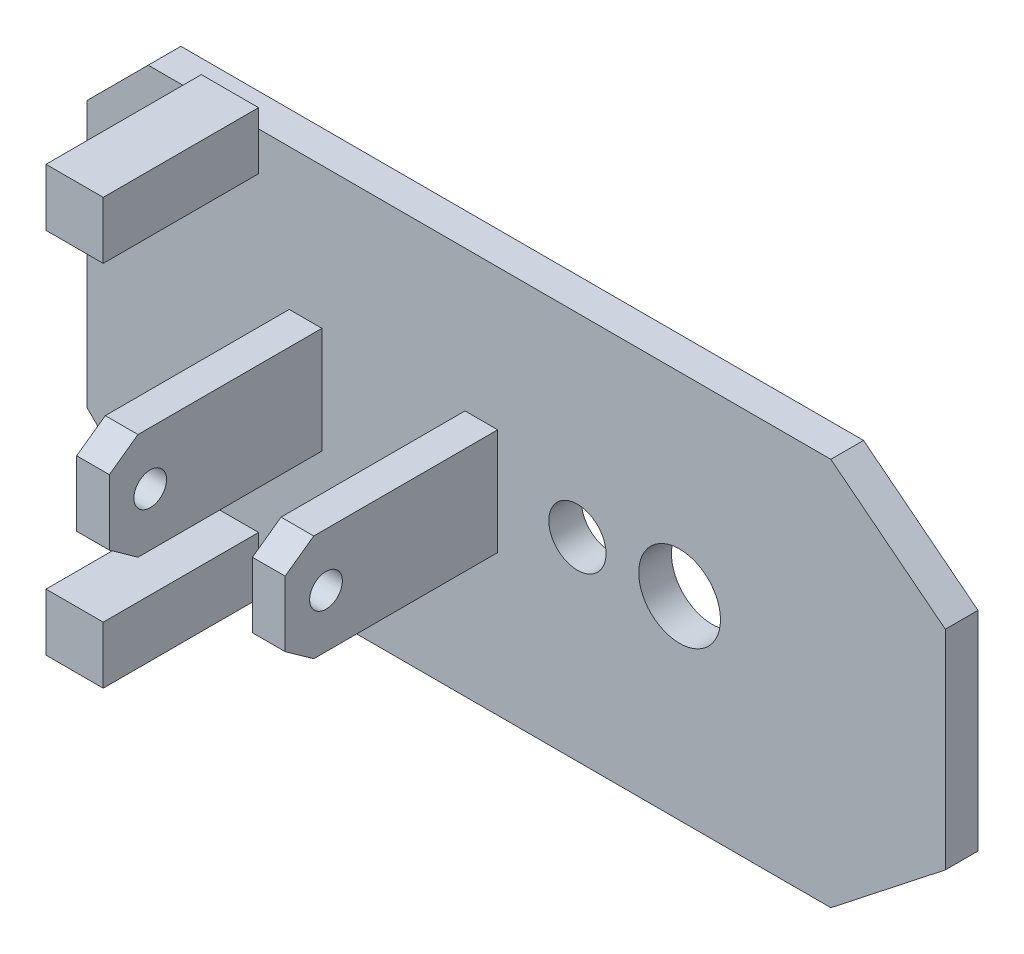
SolidWorks part; units mm, degrees
material "6061-T6 (SS)"
ref_plane "Front Plane" through (0, 0, 0) normal (0, 0, 1) x (1, 0, 0)
ref_plane "Top Plane" through (0, 0, 0) normal (0, 1, 0) x (1, 0, 0)
ref_plane "Right Plane" through (0, 0, 0) normal (1, 0, 0) x (0, 0, -1)
ref_plane "PL_Sole_Plate_base" through (0, 0, -50) normal (0, 0, 1) x (1, 0, 0)
sketch "SK_Sole_Plate" plane through (0, 0, -50) normal (0, 0, 1) x (1, 0, 0)
  line L0 (-60, 47.5) -> (107, 47.5)
  line L1 (107, 47.5) -> (135, 25.5)
  line L2 (135, 25.5) -> (135, -25.5)
  line L3 (135, -25.5) -> (107, -47.5)
  line L4 (107, -47.5) -> (-60, -47.5)
  line L5 (-60, -47.5) -> (-75, -32.5)
  line L6 (-75, -32.5) -> (-75, 32.5)
  line L7 (-75, 32.5) -> (-60, 47.5)
  circle A0 centre (70, 0) radius 10
  circle A1 centre (45, 0) radius 7
  dimension "D17_SK_Sole_Plate" = 20
  dimension "D19_SK_Sole_Plate" = 14
  dimension "P1" = 60
  dimension "P2" = 47.5
  dimension "P3" = 107
  dimension "P4" = 47.5
  dimension "P5" = 135
  dimension "P6" = 25.5
  dimension "P7" = 135
  dimension "P8" = 25.5
  dimension "P9" = 107
  dimension "P10" = 47.5
  dimension "P11" = 60
  dimension "P12" = 47.5
  dimension "P13" = 75
  dimension "P14" = 32.5
  dimension "P15" = 75
  dimension "P16" = 32.5
  dimension "P18" = 70
  dimension "P20" = 45
extrude "Sole_Plate" add sketch "SK_Sole_Plate" along normal blind 8
ref_plane "PL_Clevis_Front_base" through (17.5, 0, 0) normal (1, 0, 0) x (0, 0, -1)
sketch "SK_Clevis_Front" plane through (17.5, 0, 0) normal (1, 0, 0) x (0, 0, -1)
  line L0 (42, 13) -> (42, -13)
  line L1 (42, -13) -> (-3, -13)
  line L2 (-3, -13) -> (-10, -8)
  line L3 (-10, -8) -> (-10, 8)
  line L4 (-10, 8) -> (-3, 13)
  line L5 (-3, 13) -> (42, 13)
  circle A0 centre (0, 0) radius 4
  dimension "D13_SK_Clevis_Front" = 8
  dimension "P1" = 42
  dimension "P2" = 13
  dimension "P3" = 42
  dimension "P4" = 13
  dimension "P5" = 3
  dimension "P6" = 13
  dimension "P7" = 10
  dimension "P8" = 8
  dimension "P9" = 10
  dimension "P10" = 8
  dimension "P11" = 3
  dimension "P12" = 13
extrude "Clevis_Front" add sketch "SK_Clevis_Front" along normal blind 8
ref_plane "PL_Clevis_Back_base" through (-25.5, 0, 0) normal (1, 0, 0) x (0, 0, -1)
sketch "SK_Clevis_Back" plane through (-25.5, 0, 0) normal (1, 0, 0) x (0, 0, -1)
  line L0 (42, 13) -> (42, -13)
  line L1 (42, -13) -> (-3, -13)
  line L2 (-3, -13) -> (-10, -8)
  line L3 (-10, -8) -> (-10, 8)
  line L4 (-10, 8) -> (-3, 13)
  line L5 (-3, 13) -> (42, 13)
  circle A0 centre (0, 0) radius 4
  dimension "D13_SK_Clevis_Back" = 8
  dimension "P1" = 42
  dimension "P2" = 13
  dimension "P3" = 42
  dimension "P4" = 13
  dimension "P5" = 3
  dimension "P6" = 13
  dimension "P7" = 10
  dimension "P8" = 8
  dimension "P9" = 10
  dimension "P10" = 8
  dimension "P11" = 3
  dimension "P12" = 13
extrude "Clevis_Back" add sketch "SK_Clevis_Back" along normal blind 8
ref_plane "PL_Post_Lat_base" through (0, 0, -42) normal (0, 0, 1) x (1, 0, 0)
sketch "SK_Post_Lat" plane through (0, 0, -42) normal (0, 0, 1) x (1, 0, 0)
  line L0 (-47, -38) -> (-33, -38)
  line L1 (-33, -38) -> (-33, -52)
  line L2 (-33, -52) -> (-47, -52)
  line L3 (-47, -52) -> (-47, -38)
  dimension "P1" = 47
  dimension "P2" = 38
  dimension "P3" = 33
  dimension "P4" = 38
  dimension "P5" = 33
  dimension "P6" = 52
  dimension "P7" = 47
  dimension "P8" = 52
extrude "Post_Lat" add sketch "SK_Post_Lat" along normal blind 38
ref_plane "PL_Post_Med_base" through (0, 0, -42) normal (0, 0, 1) x (1, 0, 0)
sketch "SK_Post_Med" plane through (0, 0, -42) normal (0, 0, 1) x (1, 0, 0)
  line L0 (-47, 52) -> (-33, 52)
  line L1 (-33, 52) -> (-33, 38)
  line L2 (-33, 38) -> (-47, 38)
  line L3 (-47, 38) -> (-47, 52)
  dimension "P1" = 47
  dimension "P2" = 52
  dimension "P3" = 33
  dimension "P4" = 52
  dimension "P5" = 33
  dimension "P6" = 38
  dimension "P7" = 47
  dimension "P8" = 38
extrude "Post_Med" add sketch "SK_Post_Med" along normal blind 38
ref_axis "AX_Roll" through (-85.5, 0, 0) along (1, 0, 0)
sketch "SK_RodBalls" plane through (0, 0, 0) normal (0, 0, 1) x (1, 0, 0)
  point P0 (-40, -45)
  point P2 (-40, 45)
  dimension "P1" = 40
  dimension "P2" = 45
  dimension "P3" = 40
  dimension "P4" = 45
equation "\"Foot_length\"= 210"
equation "\"Foot_width\"= 95"
equation "\"Ankle_height\"= 50"
